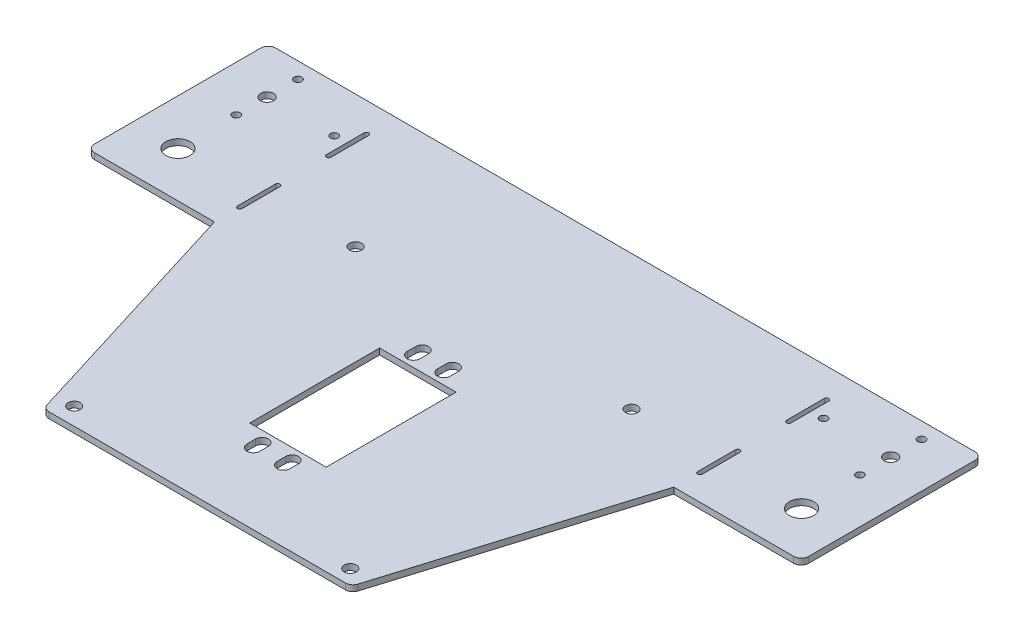
SolidWorks part; units mm, degrees
ref_plane "Front Plane" through (0, 0, 0) normal (0, 0, 1) x (1, 0, 0)
ref_plane "Top Plane" through (0, 0, 0) normal (0, 1, 0) x (1, 0, 0)
ref_plane "Right Plane" through (0, 0, 0) normal (1, 0, 0) x (0, 0, -1)
sketch "Sketch26" plane through (0, 0, 0) normal (0, 1, 0) x (1, 0, 0)
  line L0 (50.7672, 90.7668) -> (75.7672, 90.7668)
  line L1 (-76.2788, 30.7668) -> (-76.2788, 90.7668) construction
  line L2 (-0.1328, 90.7668) -> (-0.1328, -32.2411) construction
  line L3 (-49.1827, -51.0332) -> (48.9171, -51.0332)
  line L4 (-76.2788, 81.0951) -> (-76.2788, 68.5951) construction
  line L5 (-75.5288, 81.0951) -> (-75.5288, 68.5951)
  line L6 (-77.0288, 81.0951) -> (-77.0288, 68.5951)
  line L7 (-51.0328, 90.7668) -> (50.7672, 90.7668)
  line L8 (-76.2788, 39.1911) -> (-76.2788, 51.6911) construction
  line L9 (-77.0288, 39.1911) -> (-77.0288, 51.6911)
  line L10 (75.7672, 30.7668) -> (51.308, -49.2639)
  line L11 (50.7672, -61.7332) -> (50.8029, -61.7667)
  line L12 (-75.5288, 39.1911) -> (-75.5288, 51.6911)
  line L13 (-76.2788, 30.7668) -> (-51.5714, -49.2706)
  line L15 (-51.0328, 90.7668) -> (-76.2788, 90.7668)
  line L17 (117.9432, 33.2668) -> (117.9432, 88.2668)
  line L18 (75.7672, 90.7668) -> (115.4432, 90.7668)
  line L19 (-12.7878, 21.9668) -> (12.5222, 21.9668)
  line L20 (75.7672, 30.7668) -> (115.4432, 30.7668)
  line L21 (-76.2788, 30.7668) -> (-115.9548, 30.7668)
  line L22 (-12.7878, 21.9668) -> (-12.7878, -21.0332)
  line L23 (-76.2788, 90.7668) -> (-115.9548, 90.7668)
  line L24 (-118.4548, 33.2668) -> (-118.4548, 88.2668)
  line L25 (-12.7878, -21.0332) -> (12.5222, -21.0332)
  line L30 (12.5222, 21.9668) -> (12.5222, -21.0332)
  line L31 (-12.7878, 21.9668) -> (12.5222, -21.0332) construction
  line L32 (-12.7878, -21.0332) -> (12.5222, 21.9668) construction
  line L33 (76.0133, 81.0951) -> (76.0133, 68.5951) construction
  line L34 (-5.1328, 25.5668) -> (-5.1328, 28.4135) construction
  line L35 (-3.0222, 25.5668) -> (-3.0222, 28.4135)
  line L36 (-7.2433, 25.5668) -> (-7.2433, 28.4135)
  line L37 (75.2633, 81.0951) -> (75.2633, 68.5951)
  line L38 (4.8672, 25.5668) -> (4.8672, 28.4135) construction
  line L39 (2.7567, 25.5668) -> (2.7567, 28.4135)
  line L40 (6.9778, 25.5668) -> (6.9778, 28.4135)
  line L41 (-5.1328, -24.6332) -> (-5.1328, -27.4798) construction
  line L42 (-3.0222, -24.6332) -> (-3.0222, -27.4798)
  line L43 (-7.2433, -24.6332) -> (-7.2433, -27.4798)
  line L44 (4.8672, -24.6332) -> (4.8672, -27.4798) construction
  line L45 (2.7567, -24.6332) -> (2.7567, -27.4798)
  line L46 (6.9778, -24.6332) -> (6.9778, -27.4798)
  line L47 (76.7633, 81.0951) -> (76.7633, 68.5951)
  line L48 (76.0133, 39.1911) -> (76.0133, 51.6911) construction
  line L49 (76.7633, 39.1911) -> (76.7633, 51.6911)
  line L50 (75.2633, 39.1911) -> (75.2633, 51.6911)
  circle A0 centre (-45.8224, 47.0302) radius 2
  circle A1 centre (46.4306, 46.1564) radius 2
  circle A2 centre (45.5568, -46.0965) radius 2
  circle A3 centre (-46.6961, -45.2228) radius 2
  circle A4 centre (103.0672, 45.7668) radius 4
  arc A5 (117.9432, 33.2668) -> (115.4432, 30.7668) centre (115.4432, 33.2668) cw
  circle A6 centre (103.0672, 75.2668) radius 2.1413
  circle A7 centre (103.0672, 85.4668) radius 1.27
  circle A8 centre (103.0672, 65.0668) radius 1.27
  circle A9 centre (80.8672, 75.2668) radius 1.27
  arc A10 (117.9432, 88.2668) -> (115.4432, 90.7668) centre (115.4432, 88.2668) ccw
  arc A11 (-118.4548, 88.2668) -> (-115.9548, 90.7668) centre (-115.9548, 88.2668) cw
  arc A12 (-75.5288, 81.0951) -> (-77.0288, 81.0951) centre (-76.2788, 81.0951) ccw
  arc A13 (-77.0288, 68.5951) -> (-75.5288, 68.5951) centre (-76.2788, 68.5951) ccw
  arc A14 (-77.0288, 39.1911) -> (-75.5288, 39.1911) centre (-76.2788, 39.1911) ccw
  arc A15 (-75.5288, 51.6911) -> (-77.0288, 51.6911) centre (-76.2788, 51.6911) ccw
  arc A16 (-118.4548, 33.2668) -> (-115.9548, 30.7668) centre (-115.9548, 33.2668) ccw
  arc A17 (75.2633, 81.0951) -> (76.7633, 81.0951) centre (76.0133, 81.0951) cw
  arc A18 (-49.1827, -51.0332) -> (-51.5714, -49.2706) centre (-49.1827, -48.5332) cw
  arc A19 (51.308, -49.2639) -> (48.9171, -51.0332) centre (48.9171, -48.5332) cw
  arc A20 (76.7633, 68.5951) -> (75.2633, 68.5951) centre (76.0133, 68.5951) cw
  arc A21 (76.7633, 39.1911) -> (75.2633, 39.1911) centre (76.0133, 39.1911) cw
  arc A22 (75.2633, 51.6911) -> (76.7633, 51.6911) centre (76.0133, 51.6911) cw
  circle A23 centre (-81.1328, 75.2668) radius 1.27
  circle A24 centre (-103.3328, 65.0668) radius 1.27
  circle A25 centre (-103.3328, 85.4668) radius 1.27
  circle A26 centre (-103.3328, 75.2668) radius 2.1413
  circle A27 centre (-103.3328, 45.7668) radius 4
  arc A28 (-3.0222, 25.5668) -> (-7.2433, 25.5668) centre (-5.1328, 25.5668) cw
  arc A29 (-7.2433, 28.4135) -> (-3.0222, 28.4135) centre (-5.1328, 28.4135) cw
  arc A31 (2.7567, 25.5668) -> (6.9778, 25.5668) centre (4.8672, 25.5668) ccw
  arc A32 (6.9778, 28.4135) -> (2.7567, 28.4135) centre (4.8672, 28.4135) ccw
  arc A33 (-3.0222, -24.6332) -> (-7.2433, -24.6332) centre (-5.1328, -24.6332) ccw
  arc A34 (-7.2433, -27.4798) -> (-3.0222, -27.4798) centre (-5.1328, -27.4798) ccw
  arc A35 (2.7567, -24.6332) -> (6.9778, -24.6332) centre (4.8672, -24.6332) cw
  arc A36 (6.9778, -27.4798) -> (2.7567, -27.4798) centre (4.8672, -27.4798) cw
  point P26 (-0.1328, 0.4668)
  point P45 (-76.2788, 74.8451)
  point P55 (-76.2788, 45.4411)
  point P63 (76.0133, 74.8451)
  point P71 (76.0133, 45.4411)
  point P85 (-0.1328, 0.4668)
  point P95 (-5.1328, 26.9902)
  point P104 (4.8672, 26.9902)
  point P111 (-5.1328, -26.0565)
  point P118 (4.8672, -26.0565)
  dimension "D6" = 4
  dimension "D13" = 8
  dimension "D14" = 2.54
  dimension "D15" = 2.54
  dimension "D16" = 2.54
  dimension "D10" = 2.5
  dimension "D21" = 2.5
  dimension "D3" = 2.5
  dimension "D7" = 2.5
  dimension "D8" = 30
  dimension "D4" = 25
  dimension "D5" = 60
  dimension "D11" = 3.6
  dimension "D12" = 15
  dimension "D17" = 10.2
  dimension "D18" = 10.2
  dimension "D19" = 22.2
  dimension "D20" = 29.5
  dimension "D9" = 4
extrude "Boss-Extrude4" add sketch "Sketch26" along normal blind 2 contours A19 L10 L20 A5 L17 A10 L18 L0 L7 L15 L23 A11 L24 A16 L21 L13 A18 L3 L36 A29 L35 A28 A20 A15 L19 L30 L25 L22 A0 A1 region at (-0.2373, 0, -33.3649)
